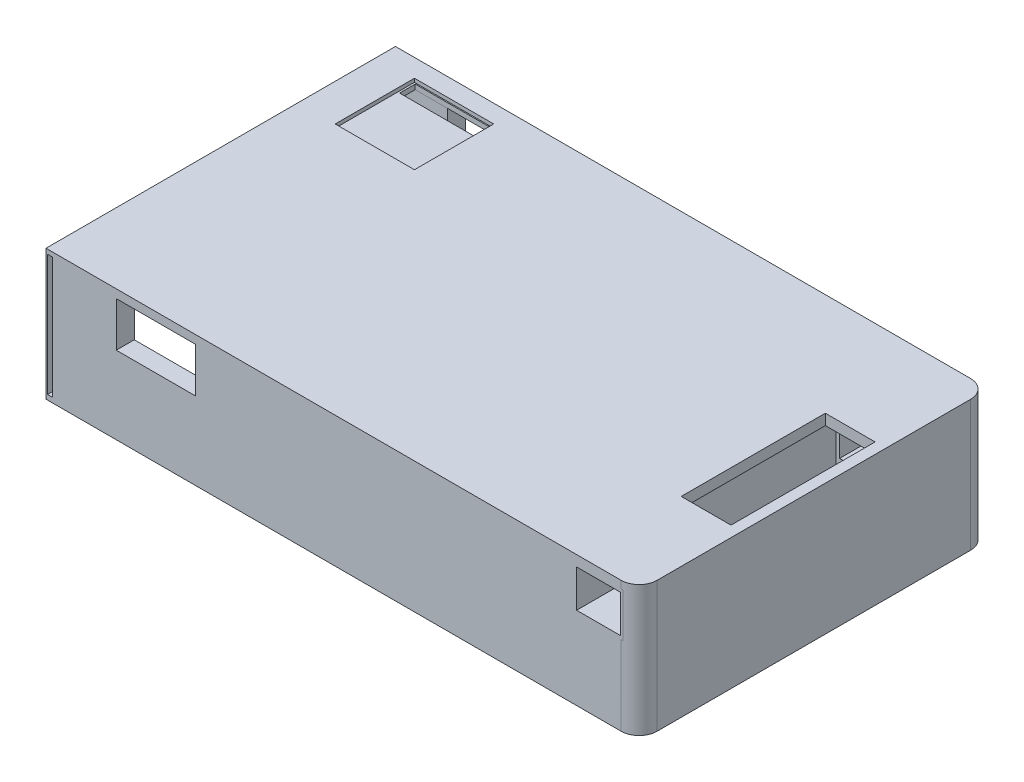
SolidWorks part; units mm, degrees
ref_plane "Alzado" through (0, 0, 0) normal (0, 0, 1) x (1, 0, 0)
ref_plane "Planta" through (0, 0, 0) normal (0, 1, 0) x (1, 0, 0)
ref_plane "Vista lateral" through (0, 0, 0) normal (1, 0, 0) x (0, 0, -1)
sketch "Croquis1" plane through (0, 0, 0) normal (0, 0, 1) x (1, 0, 0)
  line L0 (-8.5, 0) -> (8.5, 0) construction
  line L2 (57, 8.2) -> (57, -26)
  line L3 (57, -26) -> (-57, -26)
  line L4 (-57, 8.2) -> (-57, -26)
  line L5 (30.4, -16) -> (15.6, -16) construction
  line L7 (57, 8.2) -> (-57, 8.2)
  line L8 (47, 0) -> (47, -16) construction
  arc A0 (35, 3.2) -> (34, 3.2) centre (34.5, 3.2) ccw construction
  point P0 (0, 0)
  dimension "D1" = 5
  dimension "D2" = 10
  dimension "D3" = 10
extrude "Saliente-Extruir1" add sketch "Croquis1" against normal blind 97
shell "Vaciado1" thickness 5 removed face at (0, -26, -48.5)
sketch "Croquis2" plane through (0, 0, -97) normal (0, 0, -1) x (-1, 0, 0)
  line L0 (57, 8.2) -> (67.3347, 8.2)
  line L1 (67.3347, 8.2) -> (67.3347, -3.9674)
  line L2 (71.8143, 8.2) -> (71.8143, 10.2965)
  line L3 (67.3347, -26) -> (57, -26)
  line L4 (57, 8.2) -> (57, -26) construction
  line L5 (67.3347, -3.9674) -> (57, -3.9674)
  line L6 (67.3347, 8.2) -> (71.8143, 8.2)
  line L7 (71.8143, 8.2) -> (71.8143, -26)
  line L8 (71.8143, -26) -> (67.3347, -26)
  line L9 (0, 8.2) -> (0, -26) construction
  line L10 (-57, 8.2) -> (57, 8.2) construction
  line L11 (57, -26) -> (-57, -26) construction
  line L12 (71.8143, 10.2965) -> (-71.8143, 10.2965)
  line L13 (67.3347, 8.2) -> (-67.3347, 8.2)
  line L14 (-71.8143, -26) -> (-67.3347, -26)
  line L15 (-71.8143, 8.2) -> (-71.8143, -26)
  line L16 (-67.3347, 8.2) -> (-71.8143, 8.2)
  line L17 (-67.3347, -3.9674) -> (-57, -3.9674)
  line L18 (-67.3347, -26) -> (-57, -26)
  line L19 (-71.8143, 8.2) -> (-71.8143, 10.2965)
  line L20 (-67.3347, 8.2) -> (-67.3347, -3.9674)
  line L21 (-57, 8.2) -> (-67.3347, 8.2)
  point P21 (0, 10.2965)
  line M5 (57, -26) -> (57, 8.2)
  line M6 (57, 8.2) -> (-57, 8.2)
  line M7 (-57, 8.2) -> (-57, -26)
extrude "Saliente-Extruir2" add sketch "Croquis2" against normal through all contours L8 L7 L6 L1 L5 L3 M5 | L19 L16 L13 L0 L6 L2 L12 M6 | L20 L16 L15 L14 L18 L17 M7
sketch "Croquis3" plane through (0, -26, 0) normal (0, -1, 0) x (1, 0, 0)
  line L0 (0, 0) -> (0, -97) construction
  line L1 (-71.8143, 0) -> (71.8143, 0) construction
  line L2 (-71.8143, -97) -> (71.8143, -97) construction
  line L3 (-52, -5) -> (-71.8143, -5)
  line L4 (-71.8143, 0) -> (-71.8143, -97) construction
  line L5 (-52, -92) -> (-52, -5) construction
  line L6 (-68.8143, -68.5) -> (-55, -68.5)
  line L7 (-68.8143, -68.5) -> (-68.8143, -28.5)
  line L8 (-68.8143, -28.5) -> (-55, -28.5)
  line L9 (-55, -68.5) -> (-55, -28.5)
  line L10 (-68.8143, -68.5) -> (-55, -28.5) construction
  line L11 (-68.8143, -28.5) -> (-55, -68.5) construction
  line L12 (-71.8143, -48.5) -> (71.8143, -48.5) construction
  line L13 (71.8143, 0) -> (71.8143, -97) construction
  line L14 (68.8143, -28.5) -> (55, -68.5) construction
  line L15 (68.8143, -68.5) -> (55, -28.5) construction
  line L16 (55, -68.5) -> (55, -28.5)
  line L17 (68.8143, -28.5) -> (55, -28.5)
  line L18 (68.8143, -68.5) -> (68.8143, -28.5)
  line L19 (68.8143, -68.5) -> (55, -68.5)
  point P11 (-61.9071, -48.5)
  point P28 (61.9071, -48.5)
  dimension "D1" = 3
  dimension "D2" = 3
  dimension "D3" = 40
extrude "Cortar-Extruir1" cut sketch "Croquis3" against normal up to next contours L6 L9 L8 L7 | L19 L18 L17 L16
fillet "Redondeo2" radius 5 4 edges at (71.8143, -7.8517, -97) (71.8143, -7.8517, 0) (-71.8143, -7.8517, -97) (-71.8143, -7.8517, 0)
sketch "Croquis5" plane through (-71.8143, 0, 0) normal (-1, 0, 0) x (0, 0, 1)
  line L0 (-5, -10.6991) -> (2.7, -10.6991)
  line L2 (-5, -26) -> (-5, 10.2965) construction
  line L3 (2.7, -10.6991) -> (2.7, -23.7895)
  line L4 (2.7, -23.7895) -> (-5, -23.7895)
  line L5 (-5, -23.7895) -> (-5, -10.6991)
  line L6 (-48.5, -26) -> (-48.5, 10.2965) construction
  line L7 (-5, -26) -> (-92, -26) construction
  line L8 (-5, 10.2965) -> (-92, 10.2965) construction
  line L9 (-92, -23.7895) -> (-92, -10.6991)
  line L10 (-92, -10.6991) -> (-99.7, -10.6991)
  line L11 (-99.7, -10.6991) -> (-99.7, -23.7895)
  line L12 (-99.7, -23.7895) -> (-92, -23.7895)
sketch "Croquis6" plane through (0, 0, -97) normal (0, 0, -1) x (-1, 0, 0)
  line L0 (-67.3347, 8.2) -> (-57, -3.9674) construction
  line L1 (67.3347, 8.2) -> (57, -3.9674) construction
  line L2 (-60.6173, 0) -> (60.6173, 0)
  line L3 (-60.6173, 8.2) -> (-60.6173, -3.9674) construction
  line L4 (-57, 8.2) -> (-66.8143, 8.2) construction
  line L5 (-66.8143, -3.9674) -> (-57, -3.9674) construction
  line L6 (60.6173, 8.2) -> (60.6173, -3.9674) construction
  line L7 (66.8143, 8.2) -> (57, 8.2) construction
  line L8 (66.8143, -3.9674) -> (57, -3.9674) construction
  line L9 (0, 10.2965) -> (0, -26) construction
  line L10 (-66.7673, -3.0837) -> (-54.4673, -3.0837)
  line L11 (-66.7673, -3.0837) -> (-66.7673, 7.3163)
  line L12 (-66.7673, 7.3163) -> (-54.4673, 7.3163)
  line L13 (-54.4673, -3.0837) -> (-54.4673, 7.3163)
  line L14 (-60.6173, 7.3163) -> (-60.6173, -3.0837) construction
  line L15 (-66.7673, 2.1163) -> (-54.4673, 2.1163) construction
  line L16 (66.8143, 10.2965) -> (-66.8143, 10.2965) construction
  line L17 (66.8143, -26) -> (-66.8143, -26) construction
  line L18 (66.7673, 2.1163) -> (54.4673, 2.1163) construction
  line L19 (60.6173, 7.3163) -> (60.6173, -3.0837) construction
  line L20 (60.6173, 8.2) -> (60.6173, -3.9674) construction
  line L21 (67.3347, 8.2) -> (57, -3.9674) construction
  line L22 (54.4673, -3.0837) -> (54.4673, 7.3163)
  line L23 (66.7673, 7.3163) -> (54.4673, 7.3163)
  line L24 (66.7673, -3.0837) -> (66.7673, 7.3163)
  line L25 (66.7673, -3.0837) -> (54.4673, -3.0837)
  point P8 (62.1673, 2.1163)
  point P14 (0, 0)
  point P28 (-60.6173, 2.1163)
  point P46 (60.6173, 2.1163)
  dimension "D1" = 1.55
  dimension "D2" = 12.3
  dimension "D3" = 10.4
extrude "Cortar-Extruir3" cut sketch "Croquis6" against normal through all contours L22 L23 L24 L25 | L11 L12 L13 L10
sketch "Croquis7" plane through (0, 0, -97) normal (0, 0, -1) x (-1, 0, 0)
  line L0 (-57, 7.3163) -> (-57, 8.2)
  line L1 (-54.4673, -3.0837) -> (-66.6673, -3.0837)
  line L2 (-54.4673, -3.0837) -> (-54.4673, 7.325)
  line L3 (-54.4673, 7.325) -> (-66.6673, 7.325)
  line L4 (-66.6673, -3.0837) -> (-66.6673, 7.325)
  line L5 (-57, 8.2) -> (-67.3347, 8.2)
  line L6 (-67.3347, 8.2) -> (-67.3347, -3.9674)
  line L7 (-67.3347, -3.9674) -> (-57, -3.9674)
  line L8 (-57, -3.9674) -> (-57, -3.0837)
  line L9 (57, 7.3163) -> (57, 8.2)
  line L10 (54.4673, -3.0837) -> (66.6673, -3.0837)
  line L11 (54.4673, -3.0837) -> (54.4673, 7.3163)
  line L12 (54.4673, 7.3163) -> (66.6673, 7.3163)
  line L13 (66.6673, -3.0837) -> (66.6673, 7.3163)
  line L14 (57, 8.2) -> (67.3347, 8.2)
  line L15 (67.3347, 8.2) -> (67.3347, -3.9674)
  line L16 (67.3347, -3.9674) -> (57, -3.9674)
  line L17 (57, -3.9674) -> (57, -3.0837)
  line M3 (57, -3.9674) -> (57, -3.0837)
  line M7 (57, 7.3163) -> (57, 8.2)
  line M8 (57, 8.2) -> (66.8143, 8.2)
  line M12 (-66.8143, 8.2) -> (-57, 8.2)
  line M13 (-57, 8.2) -> (-57, 7.3163)
  line M17 (-57, -3.0837) -> (-57, -3.9674)
  line M18 (-57, -3.9674) -> (-66.8143, -3.9674)
  line M22 (66.8143, -3.9674) -> (57, -3.9674)
  dimension "D1" = 12.2
  dimension "D2" = 12.2
extrude "Saliente-Extruir3" add sketch "Croquis7" against normal through all contours L16 L15 L14 L12 L13 L10 M8 M7 M3 M22 | L6 L7 L1 L4 L3 L5 M18 M17 M13 M12
sketch "Croquis8" plane through (0, 10.2965, 0) normal (0, 1, 0) x (1, 0, 0)
  line L1 (-68.8143, 68.5) -> (-55, 68.5)
  line L2 (-68.8143, 68.5) -> (-68.8143, 28.5)
  line L3 (-68.8143, 28.5) -> (-55, 28.5)
  line L4 (-55, 68.5) -> (-55, 28.5)
  line L5 (55, 68.5) -> (68.8143, 68.5)
  line L6 (55, 68.5) -> (55, 28.5)
  line L7 (55, 28.5) -> (68.8143, 28.5)
  line L8 (68.8143, 68.5) -> (68.8143, 28.5)
extrude "Cortar-Extruir4" cut sketch "Croquis8" against normal through all
sketch "Croquis9" plane through (0, 3.2, 0) normal (0, -1, 0) x (1, 0, 0)
  line L0 (52, -92) -> (52, -5) construction
  line L1 (-52, -5) -> (52, -5)
  line L2 (-52, -5) -> (-52, -92)
  line L3 (-52, -92) -> (52, -92)
  line L4 (52, -5) -> (52, -92)
extrude "Cortar-Extruir5" cut sketch "Croquis9" against normal blind 10
ref_plane "Plano1" through (54.4673, -3.0837, -97) normal (-1, 0, 0) x (0, 0, 1)
sketch "Croquis11" plane through (0, -26, 0) normal (0, -1, 0) x (1, 0, 0)
  line L1 (55, -28.5) -> (53.5, -28.5)
  line L2 (55, -28.5) -> (55, -68.4995)
  line L3 (55, -68.4995) -> (53.5, -68.4995)
  line L4 (53.5, -28.5) -> (53.5, -68.4995)
  line L5 (-55, -68.5) -> (-53.5, -68.5)
  line L6 (-55, -68.5) -> (-55, -28.5)
  line L7 (-55, -28.5) -> (-53.5, -28.5)
  line L8 (-53.5, -68.5) -> (-53.5, -28.5)
  dimension "D1" = 1.5
  dimension "D2" = 1.5
extrude "Cortar-Extruir6" cut sketch "Croquis11" against normal up to vertex
sketch "Croquis13" plane through (0, -26, 0) normal (0, -1, 0) x (1, 0, 0)
  line L1 (-68.8143, -28.5) -> (-53.5, -28.5)
  line L2 (-68.8143, -28.5) -> (-68.8143, -24)
  line L3 (-68.8143, -24) -> (-53.5, -24)
  line L4 (-53.5, -28.5) -> (-53.5, -24)
  line L5 (-68.8143, -68.5) -> (-53.5, -68.5)
  line L6 (-68.8143, -68.5) -> (-68.8143, -73)
  line L7 (-68.8143, -73) -> (-53.5, -73)
  line L8 (-53.5, -68.5) -> (-53.5, -73)
  line L9 (53.5, -28.5) -> (68.8143, -28.5)
  line L10 (53.5, -28.5) -> (53.5, -24)
  line L11 (53.5, -24) -> (68.8143, -24)
  line L12 (68.8143, -28.5) -> (68.8143, -24)
  line L13 (53.5, -68.4995) -> (68.8143, -68.4995)
  line L14 (53.5, -68.4995) -> (53.5, -72.9995)
  line L15 (53.5, -72.9995) -> (68.8143, -72.9995)
  line L16 (68.8143, -68.4995) -> (68.8143, -72.9995)
  dimension "D1" = 4.5
  dimension "D2" = 4.5
  dimension "D3" = 4.5
  dimension "D4" = 4.5
extrude "Cortar-Extruir7" cut sketch "Croquis13" against normal up to surface (33.3163 mm away) up to face at (-58.4616, 7.3163, -48.5)
sketch "Croquis14" plane through (-55, 0, 0) normal (-1, 0, 0) x (0, 0, 1)
  line L4 (-68.5, 10.2965) -> (-68.5, 7.3163)
  line L5 (-68.5, 7.3163) -> (-28.5, 7.3163)
  line L6 (-28.5, 7.3163) -> (-28.5, 10.2965)
  line L7 (-28.5, 10.2965) -> (-68.5, 10.2965)
  line L8 (-68.5, 10.2965) -> (-68.5, 7.3163)
  line L9 (-68.5, 7.3163) -> (-28.5, 7.3163)
  line L10 (-28.5, 7.3163) -> (-28.5, 10.2965)
  line L11 (-28.5, 10.2965) -> (-68.5, 10.2965)
  dimension "D1" = 0
extrude "Saliente-Extruir4" add sketch "Croquis14" along normal blind 15.4989
sketch "Croquis16" plane through (-71.8143, 0, 0) normal (-1, 0, 0) x (0, 0, 1)
  line L0 (-5, 10.2965) -> (-98.4159, 10.2965)
  line L1 (-98.4159, 10.2965) -> (-98.4159, -27.1379)
  line L2 (-98.4159, -27.1379) -> (0, -27.1379)
  line L3 (0, -27.1379) -> (0, 10.2965)
  line L4 (0, 10.2965) -> (-5, 10.2965)
extrude "Cortar-Extruir8" cut sketch "Croquis16" against normal blind 20.4989
sketch "Croquis19" plane through (-51.3154, 0, 0) normal (-1, 0, 0) x (0, 0, 1)
  line L0 (0, -4.4636) -> (-5, -4.4636)
  line L1 (-92, -4.4636) -> (-97, -4.4636)
  line L2 (-5, -26) -> (-5, 10.2965) construction
  line L3 (0, 10.2965) -> (-5, 10.2965)
  line L4 (0, -26) -> (0, 10.2965)
  line L5 (0, 10.2965) -> (-5, 10.2965)
  line L6 (-5, 10.2965) -> (-5, -26)
  line L7 (-5, -26) -> (0, -26)
  line L8 (0, -26) -> (0, -4.4636)
  line L10 (-5, -4.4636) -> (-5, -26)
  line L11 (-5, -26) -> (0, -26)
  line L12 (0, 10.2965) -> (0, 7.9471)
  line L13 (-97, -26) -> (-92, -26)
  line L14 (-92, -26) -> (-92, 10.2965)
  line L15 (-92, 10.2965) -> (-97, 10.2965)
  line L16 (-97, 10.2965) -> (-97, -26)
  line L17 (-97, -26) -> (-92, -26)
  line L18 (-92, -26) -> (-92, -4.4636)
  line L20 (-97, -4.4636) -> (-97, -26)
  line L21 (0, 7.9471) -> (-5, 7.9471)
  line L22 (-5, 10.2965) -> (-5, 7.9471)
  line L23 (-97, -26) -> (-97, 10.2965) construction
  line L24 (-92, 10.2965) -> (-97, 10.2965)
  line L25 (-92, 10.2965) -> (-92, 7.9471)
  line L26 (-92, 7.9471) -> (-97, 7.9471)
  line L27 (-97, 10.2965) -> (-97, 7.9471)
  dimension "D1" = 0
  dimension "D2" = 0
extrude "Saliente-Extruir5" add sketch "Croquis19" along normal blind 22
sketch "Croquis20" plane through (-73.3154, 0, 0) normal (-1, 0, 0) x (0, 0, 1)
  line L0 (-5, -26) -> (0, -26) construction
  line L1 (0, 10.2965) -> (-5, 10.2965)
  line L2 (0, 10.2965) -> (0, -26)
  line L3 (0, -26) -> (-5, -26)
  line L4 (-5, 10.2965) -> (-5, -26)
  line L5 (-5, -4.4636) -> (-5, -26) construction
  line L7 (-92, 10.2965) -> (-97, 10.2965)
  line L8 (-92, 10.2965) -> (-92, -26)
  line L9 (-92, -26) -> (-97, -26)
  line L10 (-97, 10.2965) -> (-97, -26)
extrude "Saliente-Extruir6" add sketch "Croquis20" along normal blind 19.5
sketch "Croquis21" plane through (52, 0, 0) normal (-1, 0, 0) x (0, 0, 1)
  line L1 (-5, 10.2965) -> (-92, 10.2965)
  line L2 (-5, 10.2965) -> (-5, 7.9471)
  line L3 (-5, 7.9471) -> (-92, 7.9471)
  line L4 (-92, 10.2965) -> (-92, 7.9471)
extrude "Saliente-Extruir7" add sketch "Croquis21" along normal up to surface (144.8154 mm away) up to face at (-92.8154, -7.8517, -2.5)
sketch "Croquis23" plane through (0, 0, 0) normal (0, 0, 1) x (1, 0, 0)
  line L0 (-92.8154, 10.2965) -> (-92.8154, 7.8837) construction
  line L1 (-92.8154, -26) -> (-92.8154, 10.2965) construction
  line L3 (-92.3813, 9.0724) -> (-90.9831, 9.0724)
  line L4 (-92.3813, 9.0724) -> (-92.3813, -24.6285)
  line L5 (-92.3813, -24.6285) -> (-90.9831, -24.6285)
  line L6 (-90.9831, 9.0724) -> (-90.9831, -24.6285)
extrude "Cortar-Extruir9" cut sketch "Croquis23" against normal blind 95.5
sketch "Croquis24" plane through (0, 10.2965, 0) normal (0, 1, 0) x (1, 0, 0)
  line L0 (-92.8154, 48.5) -> (-89.7623, 48.5) construction
  line L1 (-92.8154, 0) -> (-92.8154, 97) construction
  line L2 (-89.7623, 37.3943) -> (-89.7623, 59.6057)
  line L3 (-89.7623, 59.6057) -> (-67.2686, 59.6057)
  line L4 (-67.2686, 59.6057) -> (-67.2686, 37.3943)
  line L5 (-67.2686, 37.3943) -> (-89.7623, 37.3943)
  point P7 (-89.7623, 48.5)
extrude "Cortar-Extruir10" cut sketch "Croquis24" against normal blind 1.5
sketch "Croquis25" plane through (0, 8.7965, 0) normal (0, 1, 0) x (1, 0, 0)
  line L0 (-89.7623, 59.6057) -> (-89.7623, 37.3943) construction
  line L1 (-89.7623, 40.2654) -> (-84.2178, 40.2654)
  line L2 (-89.7623, 40.2654) -> (-89.7623, 57.0137)
  line L3 (-89.7623, 57.0137) -> (-84.2178, 57.0137)
  line L4 (-84.2178, 40.2654) -> (-84.2178, 57.0137)
extrude "Cortar-Extruir11" cut sketch "Croquis25" against normal blind 1.5
sketch "Croquis26" plane through (-89.7623, 0, 0) normal (1, 0, 0) x (0, 0, -1)
  line L8 (59.6057, 10.2965) -> (37.3943, 10.2965)
  line L9 (37.3943, 10.2965) -> (37.3943, 8.7965)
  line L10 (37.3943, 8.7965) -> (40.2654, 8.7965)
  line L11 (40.2654, 8.7965) -> (40.2654, 7.9471)
  line L12 (40.2654, 7.9471) -> (57.0137, 7.9471)
  line L13 (57.0137, 7.9471) -> (57.0137, 8.7965)
  line L14 (57.0137, 8.7965) -> (59.6057, 8.7965)
  line L15 (59.6057, 8.7965) -> (59.6057, 10.2965)
  line L16 (59.6057, 10.2965) -> (37.3943, 10.2965)
  line L17 (37.3943, 10.2965) -> (37.3943, 8.7965)
  line L18 (37.3943, 8.7965) -> (40.2654, 8.7965)
  line L19 (40.2654, 8.7965) -> (40.2654, 7.9471)
  line L20 (40.2654, 7.9471) -> (57.0137, 7.9471)
  line L21 (57.0137, 7.9471) -> (57.0137, 8.7965)
  line L22 (57.0137, 8.7965) -> (59.6057, 8.7965)
  line L23 (59.6057, 8.7965) -> (59.6057, 10.2965)
  dimension "D1" = 0
extrude "Saliente-Extruir8" add sketch "Croquis26" along normal blind 46
sketch "Croquis27" plane through (0, 10.2965, 0) normal (0, 1, 0) x (1, 0, 0)
  line L0 (-90.9831, 92) -> (-73.3154, 92) construction
  line L1 (-82.5488, 92) -> (-60.5488, 92)
  line L2 (-82.5488, 92) -> (-82.5488, 70)
  line L3 (-82.5488, 70) -> (-60.5488, 70)
  line L4 (-60.5488, 92) -> (-60.5488, 70)
  dimension "D1" = 22
  dimension "D2" = 22
extrude "Cortar-Extruir12" cut sketch "Croquis27" against normal blind 1
sketch "Croquis28" plane through (0, 9.2965, 0) normal (0, 1, 0) x (1, 0, 0)
  line L1 (-60.9342, 91.7) -> (-82.0403, 91.7)
  line L2 (-60.9342, 91.7) -> (-60.9342, 87.3693)
  line L3 (-60.9342, 87.3693) -> (-82.0403, 87.3693)
  line L4 (-82.0403, 91.7) -> (-82.0403, 87.3693)
extrude "Cortar-Extruir14" cut sketch "Croquis28" against normal blind 1.5
